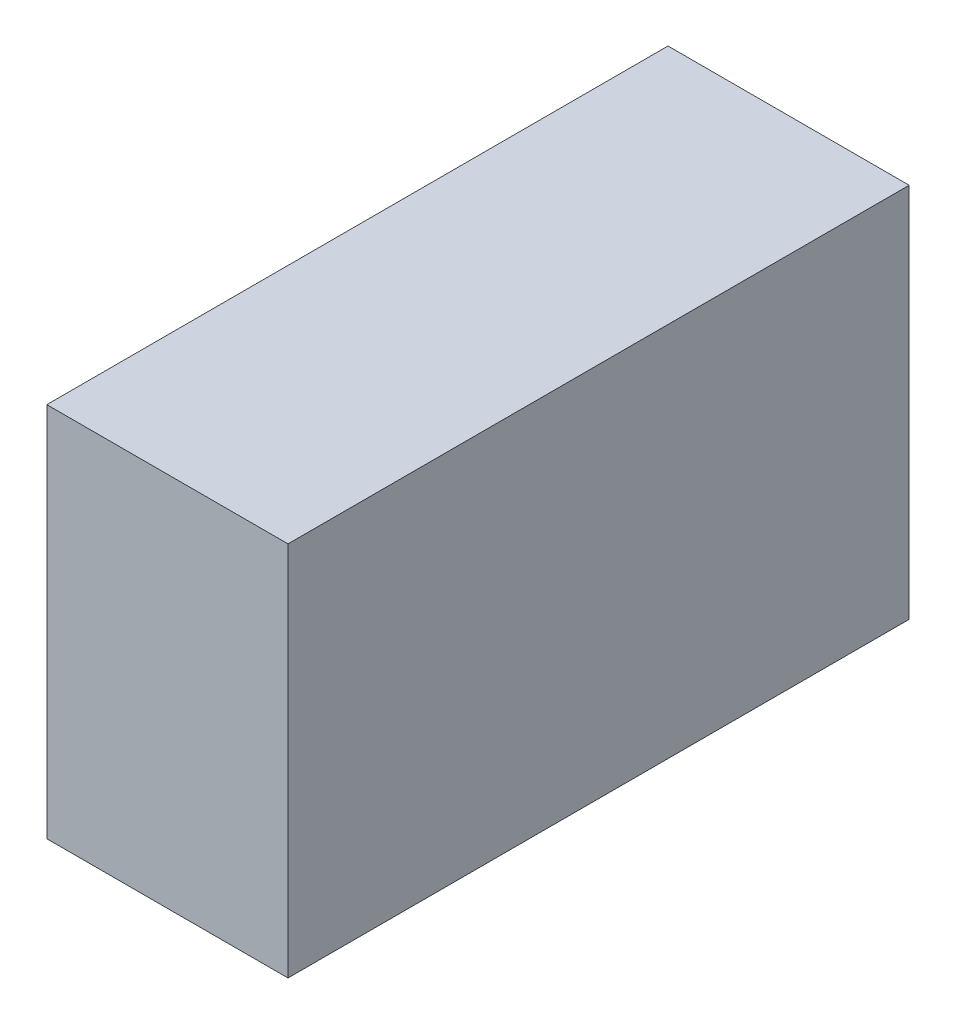
SolidWorks part; units mm, degrees
ref_plane "Front Plane" through (0, 0, 0) normal (0, 0, 1) x (1, 0, 0)
ref_plane "Top Plane" through (0, 0, 0) normal (0, 1, 0) x (1, 0, 0)
ref_plane "Right Plane" through (0, 0, 0) normal (1, 0, 0) x (0, 0, -1)
sketch "Sketch3" plane through (-13.8332, -29.1149, 26.7677) normal (0, 1, 0) x (1, 0, 0)
  line L1 (-0.1848, -0.0274) -> (0.0397, -0.0274)
  line L2 (-0.1848, -0.0274) -> (-0.1848, -0.6057)
  line L3 (-0.1848, -0.6057) -> (0.0397, -0.6057)
  line L4 (0.0397, -0.0274) -> (0.0397, -0.6057)
extrude "Boss-Extrude1" add sketch "Sketch3" along normal blind 0.175 and the other way blind 0.175
